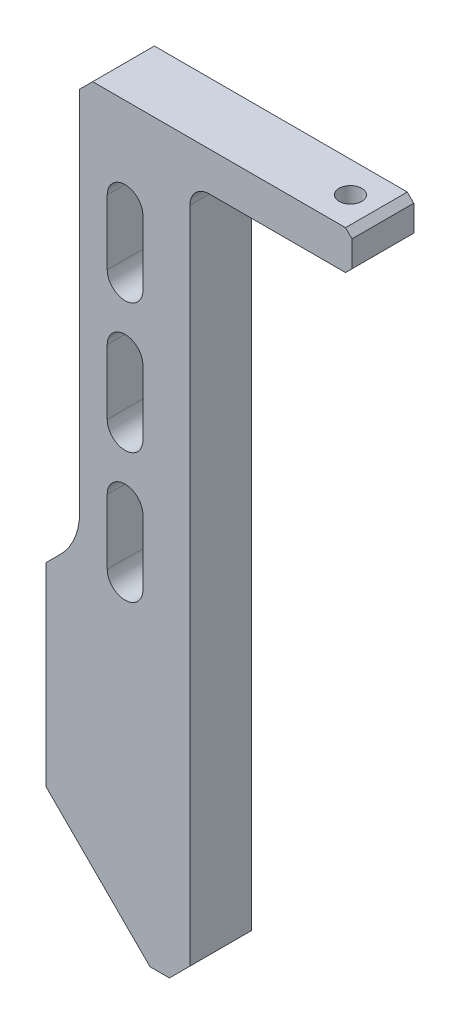
SolidWorks part; units mm, degrees
material "Plain Carbon Steel"
ref_plane "Front Plane" through (0, 0, 0) normal (0, 0, 1) x (1, 0, 0)
ref_plane "Top Plane" through (0, 0, 0) normal (0, 1, 0) x (1, 0, 0)
ref_plane "Right Plane" through (0, 0, 0) normal (1, 0, 0) x (0, 0, -1)
sketch "Sketch1" plane through (0, 0, 0) normal (0, 0, 1) x (1, 0, 0)
  line L0 (-191.4038, 11.3962) -> (-207.4038, 27.3962) construction
  line L1 (-207.4038, 27.3962) -> (-207.4038, 57.3962) construction
  line L2 (-202.2477, 62.5523) -> (-207.4038, 57.3962) construction
  line L3 (-202.2477, 125.1924) -> (-202.2477, 62.5523) construction
  line L4 (-160.2477, 125.1924) -> (-202.2477, 125.1924) construction
  line L5 (-160.2477, 119.1924) -> (-160.2477, 125.1924) construction
  line L6 (-185.2477, 119.1924) -> (-160.2477, 119.1924) construction
  line L7 (-185.2477, 119.1924) -> (-185.2477, 14.5523) construction
  line L8 (-185.2477, 14.5523) -> (-188.4038, 11.3962) construction
  line L9 (-191.4038, 11.3962) -> (-188.4038, 11.3962) construction
  line L10 (-191.4038, 11.3962) -> (-207.4038, 27.3962)
  line L11 (-207.4038, 27.3962) -> (-207.4038, 57.3962)
  line L12 (-202.2477, 62.5523) -> (-207.4038, 57.3962)
  line L13 (-202.2477, 125.1924) -> (-202.2477, 62.5523)
  line L14 (-160.2477, 125.1924) -> (-202.2477, 125.1924)
  line L15 (-160.2477, 119.1924) -> (-160.2477, 125.1924)
  line L16 (-185.2477, 119.1924) -> (-160.2477, 119.1924)
  line L17 (-185.2477, 119.1924) -> (-185.2477, 14.5523)
  line L18 (-185.2477, 14.5523) -> (-188.4038, 11.3962)
  line L19 (-191.4038, 11.3962) -> (-188.4038, 11.3962)
  line L20 (-163.7477, 125.1924) -> (-163.7477, 113.1924) construction
  line L21 (-165.2477, 125.1924) -> (-165.2477, 113.1924) construction
  line L22 (-166.7477, 125.1924) -> (-166.7477, 113.1924) construction
  line L23 (-163.7477, 125.1924) -> (-163.7477, 113.1924) construction
  line L24 (-165.2477, 125.1924) -> (-165.2477, 113.1924) construction
  line L25 (-166.7477, 125.1924) -> (-166.7477, 113.1924) construction
  line L26 (-192.4977, 61.1924) -> (-192.4977, 71.1924) construction
  line L27 (-197.9977, 61.1924) -> (-197.9977, 71.1924) construction
  line L28 (-192.4977, 81.1924) -> (-192.4977, 91.1924) construction
  line L29 (-197.9977, 81.1924) -> (-197.9977, 91.1924) construction
  line L30 (-192.4977, 101.1924) -> (-192.4977, 111.1924) construction
  line L31 (-197.9977, 101.1924) -> (-197.9977, 111.1924) construction
  line L32 (-192.4977, 61.1924) -> (-192.4977, 71.1924)
  line L33 (-197.9977, 61.1924) -> (-197.9977, 71.1924)
  line L34 (-192.4977, 81.1924) -> (-192.4977, 91.1924)
  line L35 (-197.9977, 81.1924) -> (-197.9977, 91.1924)
  line L36 (-192.4977, 101.1924) -> (-192.4977, 111.1924)
  line L37 (-197.9977, 101.1924) -> (-197.9977, 111.1924)
  arc A0 (-192.4977, 71.1924) -> (-197.9977, 71.1924) centre (-195.2477, 71.1924) ccw construction
  arc A1 (-197.9977, 61.1924) -> (-192.4977, 61.1924) centre (-195.2477, 61.1924) ccw construction
  arc A2 (-192.4977, 91.1924) -> (-197.9977, 91.1924) centre (-195.2477, 91.1924) ccw construction
  arc A3 (-197.9977, 81.1924) -> (-192.4977, 81.1924) centre (-195.2477, 81.1924) ccw construction
  arc A4 (-192.4977, 111.1924) -> (-197.9977, 111.1924) centre (-195.2477, 111.1924) ccw construction
  arc A5 (-197.9977, 101.1924) -> (-192.4977, 101.1924) centre (-195.2477, 101.1924) ccw construction
  arc A6 (-192.4977, 71.1924) -> (-197.9977, 71.1924) centre (-195.2477, 71.1924) ccw
  arc A7 (-197.9977, 61.1924) -> (-192.4977, 61.1924) centre (-195.2477, 61.1924) ccw
  arc A8 (-192.4977, 91.1924) -> (-197.9977, 91.1924) centre (-195.2477, 91.1924) ccw
  arc A9 (-197.9977, 81.1924) -> (-192.4977, 81.1924) centre (-195.2477, 81.1924) ccw
  arc A10 (-192.4977, 111.1924) -> (-197.9977, 111.1924) centre (-195.2477, 111.1924) ccw
  arc A11 (-197.9977, 101.1924) -> (-192.4977, 101.1924) centre (-195.2477, 101.1924) ccw
extrude "Boss-Extrude1" add sketch "Sketch1" along normal blind 4.7625 and the other way blind 4.7625
sketch "Sketch2" plane through (0, 125.1924, 0) normal (0, 1, 0) x (-1, 0, 0)
  circle A0 centre (165.2477, 0) radius 1.75
  dimension "D1" = 3.5
extrude "Cut-Extrude1" cut sketch "Sketch2" against normal through all
fillet "Fillet1" radius 10 1 edges at (-202.2477, 62.5523, 0)
chamfer "Chamfer1" distance 2 angle 45 1 edges at (-202.2477, 125.1924, 0)
chamfer "Chamfer2" distance 1 angle 45 2 edges at (-160.2477, 125.1924, 0) (-160.2477, 119.1924, 0)
fillet "Fillet2" radius 3 1 edges at (-185.2477, 119.1924, 0)
